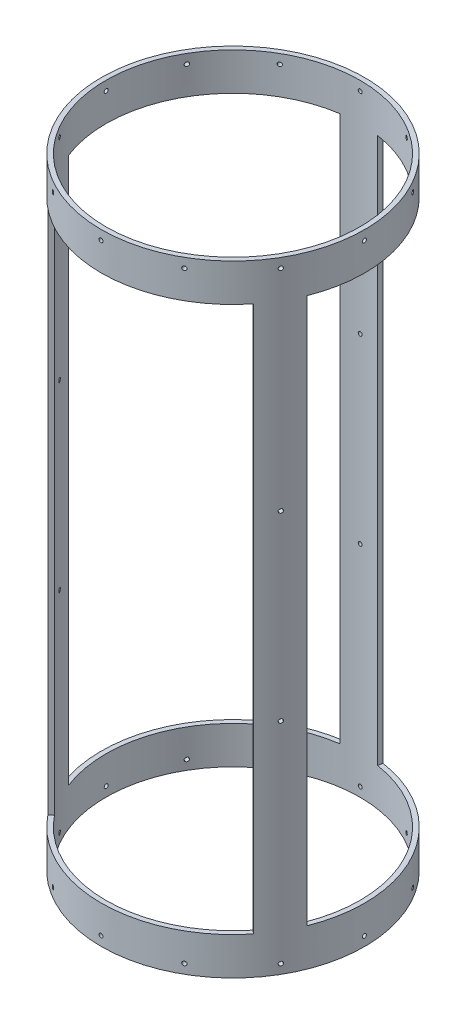
SolidWorks part; units mm, degrees
material "6061-T6 (SS)"
ref_plane "Front Plane" through (0, 0, 0) normal (0, 0, 1) x (1, 0, 0)
ref_plane "Top Plane" through (0, 0, 0) normal (0, 1, 0) x (1, 0, 0)
ref_plane "Right Plane" through (0, 0, 0) normal (1, 0, 0) x (0, 0, -1)
sketch "Sketch1" plane through (0, 0, 0) normal (0, 1, 0) x (1, 0, 0)
  circle A0 centre (0, 0) radius 88.9
  circle A1 centre (0, 0) radius 85.725
  dimension "D1" = 177.8
  dimension "D2" = 171.45
extrude "Boss-Extrude1" add sketch "Sketch1" along normal mid plane 419.1
sketch "Sketch6" plane through (0, -209.55, 0) normal (0, -1, 0) x (-1, 0, 0)
  line L0 (82.7901, -32.3885) -> (79.8333, -31.2317)
  line L1 (13.1222, 87.9262) -> (12.6536, 84.786)
  line L2 (0, 0) -> (0, 85.725) construction
  line L3 (-97.8543, 0) -> (97.8543, 0) construction
  line L4 (0, 0) -> (12.6536, 84.786) construction
  arc A0 (13.1222, 87.9262) -> (82.7901, -32.3885) centre (0, 0) cw
  circle A1 centre (0, 0) radius 88.9 construction
  arc A2 (12.6536, 84.786) -> (79.8333, -31.2317) centre (0, 0) cw
  circle A3 centre (0, 0) radius 85.725 construction
  arc A4 (0, 85.725) -> (12.6536, 84.786) centre (0, 0) cw construction
  dimension "D1" = 153.924
  dimension "D2" = 12.7
extrude "Cut-Extrude5" cut sketch "Sketch6" against normal offset from surface (368.3 mm away) 25.4 from offset 25.4 up to face at (0, 209.55, 88.9) offset against normal yes
pattern_circular "CirPattern5" count 3 over 360 about axis through (0, -209.55, 0) along (0, 1, 0) of "Cut-Extrude5"
ref_plane "Plane1" through (0, 0, -88.9) normal (0, 0, -1) x (-1, 0, 0)
sketch "Sketch3" plane through (0, 0, 0) normal (0, 0, -1) x (-1, 0, 0)
  line L1 (-88.9, -209.55) -> (88.9, -209.55) construction
  line L3 (-12.8692, 184.15) -> (-12.8692, -184.15) construction
  circle A0 centre (-0.1692, -203.2) radius 1.3525
  dimension "D1" = 6.35
  dimension "D2" = 2.7051
  dimension "D4" = 12.7
extrude "Cut-Extrude2" cut sketch "Sketch3" along normal up to surface (88.8921 mm away) up to face at (-0.0918, 0, 72.1578)
pattern_circular "CirPattern2" count 12 over 360 about axis through (0, 209.55, 0) along (0, -1, 0) of "Cut-Extrude2" reverse direction yes
sketch "Sketch4" plane through (0, 0, -88.9) normal (0, 0, -1) x (-1, 0, 0)
  line L1 (88.9, 209.55) -> (-88.9, 209.55) construction
  circle A0 centre (-0.1692, 203.2) radius 1.3525
  dimension "D1" = 2.7051
  dimension "D2" = 6.35
extrude "Cut-Extrude3" cut sketch "Sketch4" against normal blind 15.24
pattern_circular "CirPattern3" count 12 over 360 about axis through (0, 209.55, 0) along (0, 1, 0) of "Cut-Extrude3"
ref_plane "Plane2" through (0, 0, 88.9) normal (0, 0, 1) x (1, 0, 0)
sketch "Sketch5" plane through (0, 0, 88.9) normal (0, 0, 1) x (1, 0, 0)
  line L0 (-88.9, 184.15) -> (-13.1222, 184.15) construction
  line L1 (88.9, -184.15) -> (13.3458, -184.15) construction
  circle A0 centre (0.1692, 61.3833) radius 1.3526
  circle A1 centre (0.1692, -61.3833) radius 1.3526
  dimension "D1" = 122.7667
  dimension "D2" = 122.7667
  dimension "D3" = 2.7051
  dimension "D4" = 2.7051
extrude "Cut-Extrude4" cut sketch "Sketch5" against normal up to surface (177.787 mm away) up to face at (-77.2806, 202.5938, -43.9383)
pattern_circular "CirPattern4" count 3 over 360 about axis through (0, 209.55, 0) along (0, -1, 0) of "Cut-Extrude4"
